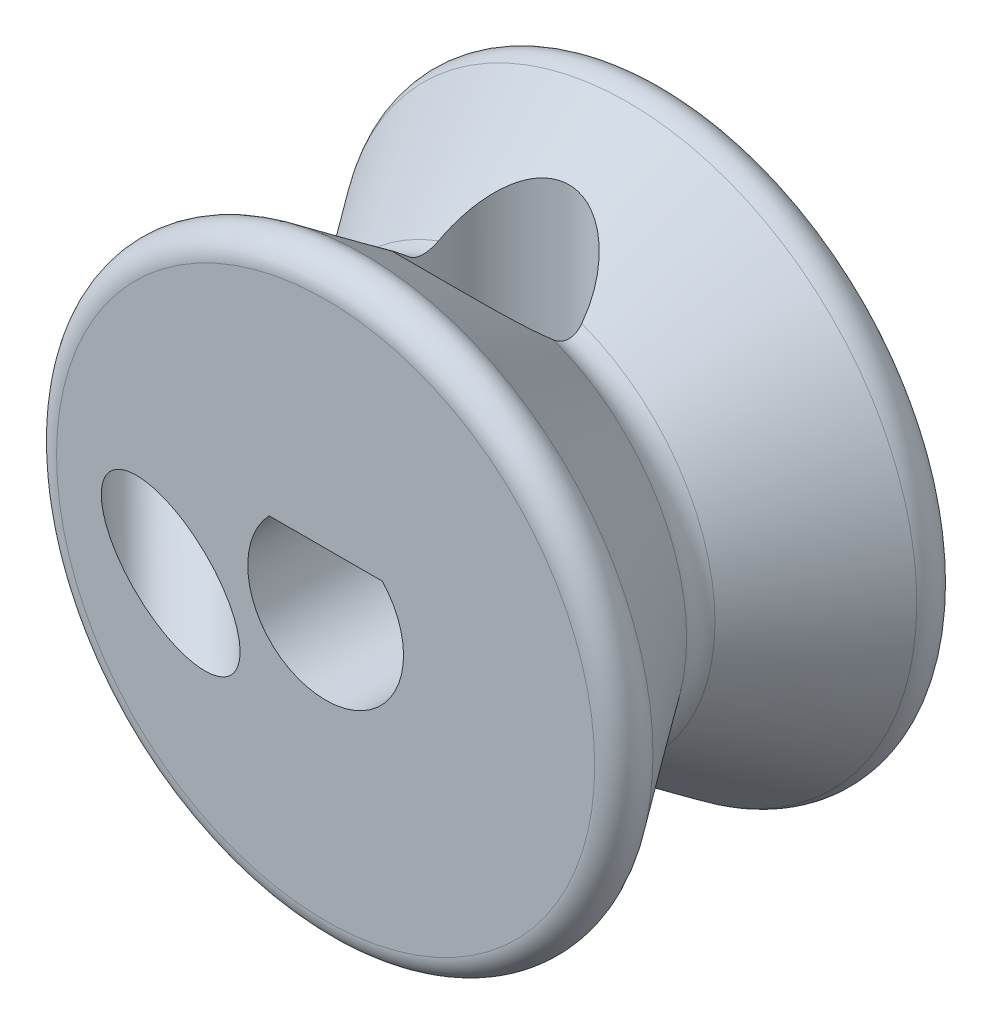
SolidWorks part; units mm, degrees
ref_plane "Front Plane" through (0, 0, 0) normal (0, 0, 1) x (1, 0, 0)
ref_plane "Top Plane" through (0, 0, 0) normal (0, 1, 0) x (1, 0, 0)
ref_plane "Right Plane" through (0, 0, 0) normal (1, 0, 0) x (0, 0, -1)
sketch "Sketch3" plane through (0, 0, 0) normal (1, 0, 0) x (0, 0, -1)
  line L0 (0, 0) -> (7, 0)
  line L1 (0, 0) -> (0, 5.5284)
  line L3 (0.7906, 5.9353) -> (3.2094, 4.2076)
  line L4 (3.7906, 4.2076) -> (6.2094, 5.9353)
  line L5 (7, 5.5284) -> (7, 0)
  arc A0 (6.2094, 5.9353) -> (7, 5.5284) centre (6.5, 5.5284) cw
  arc A1 (3.2094, 4.2076) -> (3.7906, 4.2076) centre (3.5, 4.6145) ccw
  arc A2 (0, 5.5284) -> (0.7906, 5.9353) centre (0.5, 5.5284) cw
  point P3 (0, 0)
  point P9 (3.5, 0)
  point P10 (0, 0)
  point P13 (7, 6.5)
  point P16 (3.5, 4)
  point P19 (0, 6.5)
  dimension "D4" = 0.5
  dimension "D1" = 7
  dimension "D2" = 6.5
  dimension "D3" = 4
revolve "Revolve1" add sketch "Sketch3" angle 360 about L0
sketch "Sketch4" plane through (0, 0, 0) normal (0, 0, 1) x (1, 0, 0)
  line L0 (-1.1619, 1.1) -> (1.1619, 1.1)
  arc A0 (-1.1619, 1.1) -> (1.1619, 1.1) centre (0, 0) ccw
  dimension "D1" = 3.2
  dimension "D2" = 1.1
extrude "Cut-Extrude1" cut sketch "Sketch4" against normal blind 7
sketch "Sketch5" plane through (0, 1.1, 0) normal (0, -1, 0) x (1, 0, 0)
  line L0 (0, 0) -> (0, -7) construction
  line L1 (-5.5284, -7) -> (5.5284, -7) construction
  circle A0 centre (0, -3.5) radius 1.5
  dimension "D1" = 3
extrude "Cut-Extrude2" cut sketch "Sketch5" against normal blind 7 and the other way blind 0.5
ref_plane "Plane2" through (-3.5181, 3.3307, -2.3176) normal (-0.5909, 0.5594, -0.5812) x (-0.4221, 0.3996, 0.8137)
sketch "Sketch6" plane through (-3.5181, 3.3307, -2.3176) normal (-0.5909, 0.5594, -0.5812) x (-0.4221, 0.3996, 0.8137)
  circle A0 centre (0.0417, -2.8652) radius 1
  ellipse E0 centre (-3.5416, 0) end of major axis (-3.5416, -4.2076) minor radius 2.4456 (-2.5875, 3.8742) -> (-1.3453, 1.8508) ccw construction
  dimension "D1" = 2
  dimension "D2" = 3.5832
  dimension "D3" = 4.716
extrude "Cut-Extrude3" cut sketch "Sketch6" against normal through all
